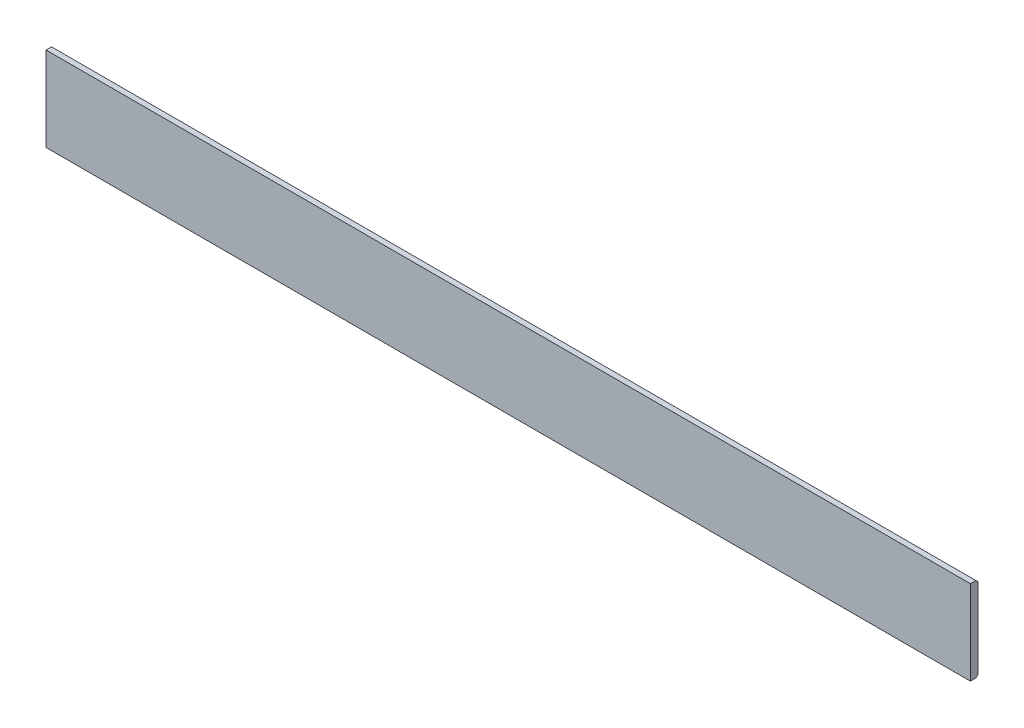
SolidWorks part; units mm, degrees
ref_plane "前视基准面" through (0, 0, 0) normal (0, 0, 1) x (1, 0, 0)
ref_plane "上视基准面" through (0, 0, 0) normal (0, 1, 0) x (1, 0, 0)
ref_plane "右视基准面" through (0, 0, 0) normal (1, 0, 0) x (0, 0, -1)
sketch "草图1" plane through (0, 0, 0) normal (0, 0, 1) x (1, 0, 0)
  line L1 (-1095, 100) -> (1095, 100)
  line L2 (-1095, 100) -> (-1095, -100)
  line L3 (-1095, -100) -> (1095, -100)
  line L4 (1095, 100) -> (1095, -100)
  line L5 (-1095, 100) -> (1095, -100) construction
  line L6 (-1095, -100) -> (1095, 100) construction
  point P0 (0, 0)
  dimension "D1" = 200
  dimension "D2" = 2190
base flange "基体-法兰1" sketch "草图1" thickness 18 reverse thickness direction no parameters "D1"=1
chamfer "倒角1" distance 5 angle 45 2 edges at (0, -100, -18) (0, 100, -18)
sketch "折弯-线1" plane through (0, 0, 0) normal (0, 1, 0) x (1, 0, 0)
sketch "边界框1" plane through (0, 0, 0) normal (0, 1, 0) x (1, 0, 0)
sheet metal parameters "钣金6" thickness 18 parameters "D1"=1
flat pattern "平板型式6" [suppressed]
sketch "折弯-线2" plane through (0, 0, 0) normal (0, 1, 0) x (1, 0, 0)
sketch "边界框2" [suppressed] plane through (0, 0, 0) normal (0, 1, 0) x (1, 0, 0)
